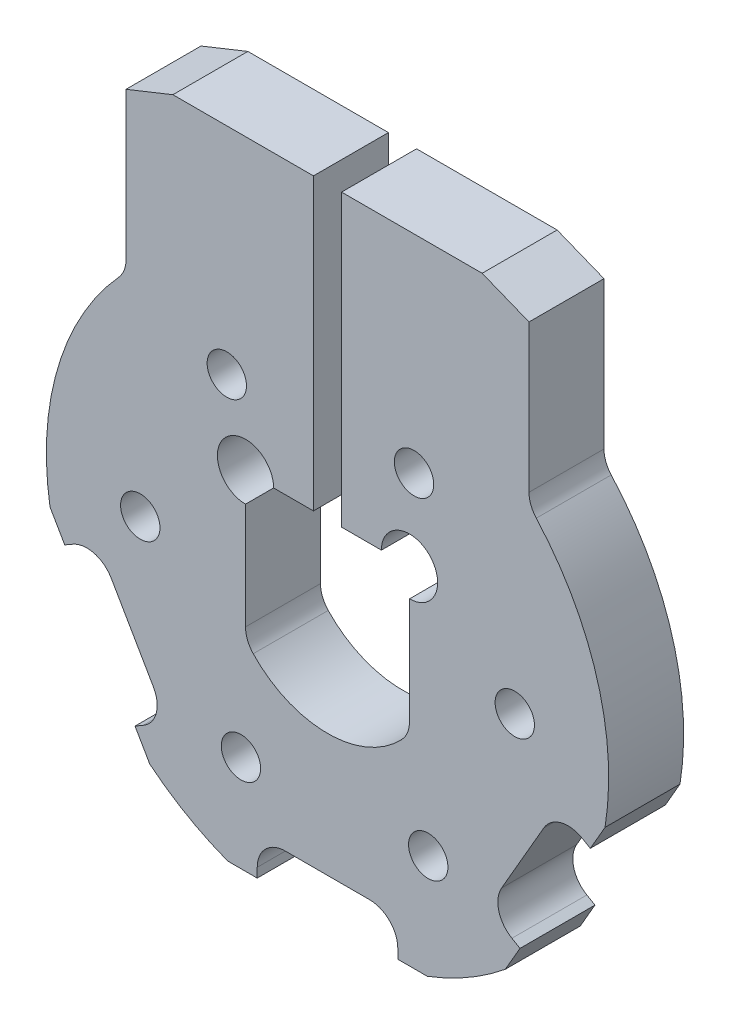
SolidWorks part; units mm, degrees
material "7075-T6 (SN)"
ref_plane "Ebene vorne" through (0, 0, 0) normal (0, 0, 1) x (1, 0, 0)
ref_plane "Ebene oben" through (0, 0, 0) normal (0, 1, 0) x (1, 0, 0)
ref_plane "Ebene rechts" through (0, 0, 0) normal (1, 0, 0) x (0, 0, -1)
sketch "Skizze1" plane through (0, 0, 0) normal (0, 0, 1) x (1, 0, 0)
  line L0 (4.6759, -29.3167) -> (-4.3241, -29.3167)
  line L1 (-7.3241, -32.3167) -> (-7.3241, -33.3167)
  line L2 (-7.3241, -33.3167) -> (-10.4705, -33.3167)
  line L3 (-18.7907, -28.513) -> (-20.3639, -25.7882)
  line L4 (-20.3639, -25.7882) -> (-19.4978, -25.2882)
  line L5 (-18.3998, -21.1901) -> (-22.8998, -13.3959)
  line L6 (-26.9978, -12.2978) -> (-27.8639, -12.7978)
  line L7 (-27.8639, -12.7978) -> (-29.437, -10.073)
  line L8 (-21.3241, 16.8384) -> (-21.3241, 32.5763)
  line L9 (-21.3241, 32.5763) -> (-16.3241, 34.5763)
  line L10 (-16.3241, 34.5763) -> (-1.3241, 34.5763)
  line L11 (-1.3241, 34.5763) -> (-1.3241, 3.6138)
  line L12 (-1.3241, 3.6138) -> (-5.5741, 3.6138)
  line L13 (-8.5741, 0.6138) -> (-8.5741, -10.7286)
  line L14 (8.9259, -10.7286) -> (8.9259, 0.6138)
  line L15 (5.9259, 3.6138) -> (1.6759, 3.6138)
  line L16 (1.6759, 3.6138) -> (1.6759, 34.5763)
  line L17 (1.6759, 34.5763) -> (16.6759, 34.5763)
  line L18 (16.6759, 34.5763) -> (21.6759, 32.5763)
  line L19 (21.6759, 32.5763) -> (21.6759, 16.8384)
  line L20 (29.7888, -10.073) -> (28.2156, -12.7978)
  line L21 (28.2156, -12.7978) -> (27.3496, -12.2978)
  line L22 (23.2515, -13.3959) -> (18.7515, -21.1901)
  line L23 (19.8496, -25.2882) -> (20.7156, -25.7882)
  line L24 (20.7156, -25.7882) -> (19.1424, -28.513)
  line L25 (10.8222, -33.3167) -> (7.6759, -33.3167)
  line L26 (7.6759, -33.3167) -> (7.6759, -32.3167)
  circle A0 centre (9.4108, 12.4709) radius 2.1
  circle A1 centre (20.1568, -4.3969) radius 2.1
  circle A2 centre (10.9219, -22.1371) radius 2.1
  circle A3 centre (-9.0591, -23.0095) radius 2.1
  circle A4 centre (-10.5701, 11.5985) radius 2.1
  circle A5 centre (-19.8051, -6.1417) radius 2.1
  arc A6 (-4.3241, -29.3167) -> (-7.3241, -32.3167) centre (-4.3241, -32.3167) ccw
  arc A7 (-18.7907, -28.513) -> (-10.4705, -33.3167) centre (0.1759, -5.2693) ccw
  arc A8 (-19.4978, -25.2882) -> (-18.3998, -21.1901) centre (-20.9978, -22.6901) ccw
  arc A9 (-22.8998, -13.3959) -> (-26.9978, -12.2978) centre (-25.4978, -14.8959) ccw
  arc A10 (-22.0968, 14.8286) -> (-29.437, -10.073) centre (0.1759, -5.2693) ccw
  arc A11 (-22.0968, 14.8286) -> (-21.3241, 16.8384) centre (-24.3241, 16.8384) ccw
  arc A12 (-5.5741, 3.6138) -> (-8.5741, 0.6138) centre (-8.5741, 3.6138) ccw
  arc A13 (-8.5741, -10.7286) -> (-7.7497, -12.7943) centre (-5.5741, -10.7286) ccw
  arc A14 (-7.7497, -12.7943) -> (8.1015, -12.7943) centre (0.1759, -5.2693) ccw
  arc A15 (8.1015, -12.7943) -> (8.9259, -10.7286) centre (5.9259, -10.7286) ccw
  arc A16 (8.9259, 0.6138) -> (5.9259, 3.6138) centre (8.9259, 3.6138) ccw
  arc A17 (21.6759, 16.8384) -> (22.4486, 14.8286) centre (24.6759, 16.8384) ccw
  arc A18 (29.7888, -10.073) -> (22.4486, 14.8286) centre (0.1759, -5.2693) ccw
  arc A19 (27.3496, -12.2978) -> (23.2515, -13.3959) centre (25.8496, -14.8959) ccw
  arc A20 (18.7515, -21.1901) -> (19.8496, -25.2882) centre (21.3496, -22.6901) ccw
  arc A21 (10.8222, -33.3167) -> (19.1424, -28.513) centre (0.1759, -5.2693) ccw
  arc A22 (7.6759, -32.3167) -> (4.6759, -29.3167) centre (4.6759, -32.3167) ccw
extrude "Aufsatz-Linear austragen1" add sketch "Skizze1" along normal blind 8
